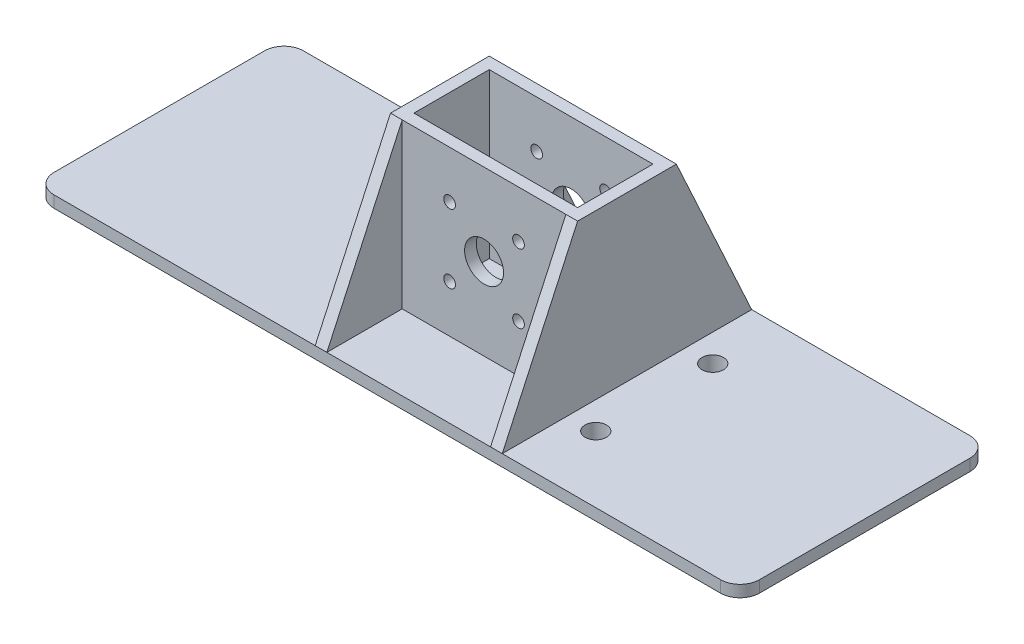
SolidWorks part; units mm, degrees
material "ABS"
ref_plane "Front Plane" through (0, 0, 0) normal (0, 0, 1) x (1, 0, 0)
ref_plane "Top Plane" through (0, 0, 0) normal (0, 1, 0) x (1, 0, 0)
ref_plane "Right Plane" through (0, 0, 0) normal (1, 0, 0) x (0, 0, -1)
sketch "Sketch1" plane through (0, 0, 0) normal (0, 1, 0) x (1, 0, 0)
  line L1 (85.5, 32) -> (-85.5, 32)
  line L2 (90.5, 27) -> (90.5, -27)
  line L3 (85.5, -32) -> (-85.5, -32)
  line L4 (-90.5, 27) -> (-90.5, -27)
  line L5 (90.5, 32) -> (-90.5, -32) construction
  line L6 (90.5, -32) -> (-90.5, 32) construction
  arc A0 (85.5, 32) -> (90.5, 27) centre (85.5, 27) cw
  arc A1 (90.5, -27) -> (85.5, -32) centre (85.5, -27) cw
  arc A2 (-85.5, -32) -> (-90.5, -27) centre (-85.5, -27) cw
  arc A3 (-85.5, 32) -> (-90.5, 27) centre (-85.5, 27) ccw
  point P0 (0, 0)
  dimension "D1" = 5
  dimension "D2" = 181
  dimension "D3" = 64
extrude "Boss-Extrude1" add sketch "Sketch1" along normal blind 3
sketch "Sketch2" plane through (0, 3, 0) normal (0, 1, 0) x (1, 0, 0)
  line L0 (-90.5, 0) -> (90.5, 0) construction
  line L1 (-90.5, 27) -> (-90.5, -27) construction
  line L2 (90.5, -27) -> (90.5, 27) construction
  circle A0 centre (36.5, -15) radius 2.75
  circle A1 centre (36.5, 15) radius 2.75
  circle A2 centre (-25.5, 0) radius 2.75
  dimension "D1" = 30
  dimension "D3" = 5.5
  dimension "D4" = 62
  dimension "D2" = 127
extrude "Cut-Extrude1" cut sketch "Sketch2" against normal through all
sketch "Sketch9" plane through (0, 0, 0) normal (0, -1, 0) x (1, 0, 0)
  circle A0 centre (-25.5, 0) radius 4.75
  circle A1 centre (36.5, -15) radius 4.75
  circle A2 centre (36.5, 15) radius 4.75
  circle A3 centre (-25.5, 0) radius 2.75
  circle A4 centre (36.5, 15) radius 2.75
  circle A5 centre (36.5, -15) radius 2.75
  dimension "D1" = 9.5
  dimension "D2" = 9.5
  dimension "D3" = 9.5
extrude "Boss-Extrude4" add sketch "Sketch9" along normal blind 4.5
sketch "Sketch11" plane through (0, 3, 0) normal (0, 1, 0) x (1, 0, 0)
  line L0 (85.5, 32) -> (-85.5, 32) construction
  line L1 (-18.5, 32) -> (-15.5, 32)
  line L2 (-18.5, 32) -> (-18.5, -32)
  line L3 (-18.5, -32) -> (-15.5, -32)
  line L4 (29.5, 32) -> (29.5, -32)
  line L5 (-85.5, -32) -> (85.5, -32) construction
  line L6 (-25.5, 0) -> (-18.5, 0) construction
  line L7 (26.5, 32) -> (29.5, 32)
  line L8 (36.5, -15) -> (29.5, -15) construction
  line L9 (-15.5, 9.6667) -> (26.5, 9.6667)
  line L10 (-15.5, 9.6667) -> (-15.5, -9.6667)
  line L11 (-15.5, -9.6667) -> (26.5, -9.6667)
  line L12 (26.5, 9.6667) -> (26.5, -9.6667)
  line L14 (-15.5, 32) -> (-15.5, 12.6667)
  line L15 (-15.5, 12.6667) -> (26.5, 12.6667)
  line L16 (26.5, 32) -> (26.5, 12.6667)
  line L18 (-15.5, -32) -> (-15.5, -12.6667)
  line L19 (-15.5, -12.6667) -> (26.5, -12.6667)
  line L20 (26.5, -32) -> (26.5, -12.6667)
  line L21 (26.5, -32) -> (29.5, -32)
  point P21 (26.5, 0)
  point P22 (29.5, 0)
  dimension "D1" = 42
  dimension "D2" = 3
  dimension "D3" = 3
  dimension "D4" = 3
extrude "Boss-Extrude6" add sketch "Sketch11" along normal blind 42
sketch "Sketch12" plane through (-15.5, 0, 0) normal (1, 0, 0) x (0, 0, -1)
  line L0 (-12.6667, 45) -> (-32, 3)
  line L1 (-32, 3) -> (-32, 45)
  line L2 (-32, 45) -> (-12.6667, 45)
  line L3 (12.6667, 45) -> (32, 3)
  line L4 (32, 3) -> (32, 45)
  line L5 (32, 45) -> (12.6667, 45)
extrude "Cut-Extrude2" cut sketch "Sketch12" against normal through all both and the other way through all
sketch "Sketch13" plane through (0, 0, 12.6667) normal (0, 0, 1) x (1, 0, 0)
  line L0 (5.5, 45) -> (5.5, 3) construction
  line L1 (-15.5, 45) -> (26.5, 45) construction
  line L2 (-15.5, 3) -> (26.5, 3) construction
  line L3 (-15.5, 24) -> (26.5, 24) construction
  line L4 (-15.5, 45) -> (-15.5, 3) construction
  line L5 (26.5, 45) -> (26.5, 3) construction
  line L6 (-3.3388, 15.1612) -> (5.5, 24) construction
  circle A0 centre (5.5, 24) radius 5
  circle A1 centre (-3.3388, 15.1612) radius 1.5
  circle A2 centre (-3.3388, 32.8388) radius 1.5
  circle A3 centre (14.3388, 15.1612) radius 1.5
  circle A4 centre (14.3388, 32.8388) radius 1.5
  point P10 (5.5, 24)
  point P11 (5.5, 24)
  dimension "D1" = 10
  dimension "D2" = 12.5
  dimension "D3" = 3
  dimension "D4" = 45
extrude "Cut-Extrude3" cut sketch "Sketch13" against normal through all both
